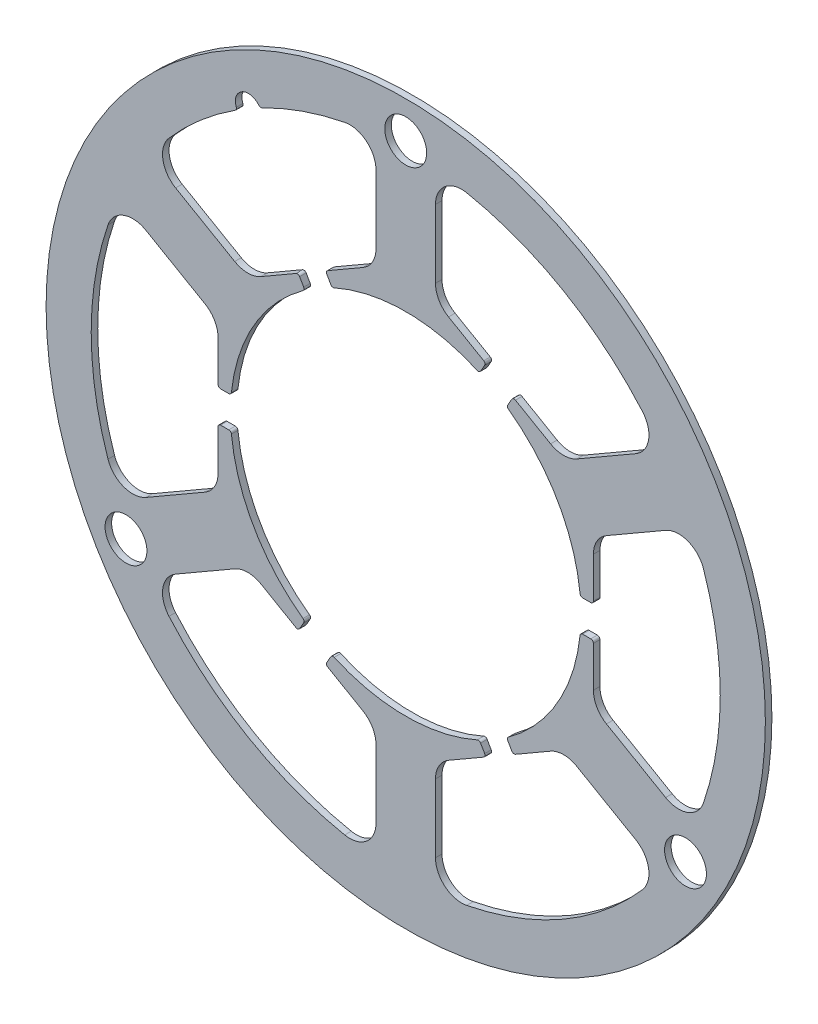
SolidWorks part; units mm, degrees
ref_plane "Ön Düzlem" through (0, 0, 0) normal (0, 0, 1) x (1, 0, 0)
ref_plane "Üst Düzlem" through (0, 0, 0) normal (0, 1, 0) x (1, 0, 0)
ref_plane "Sağ Düzlem" through (0, 0, 0) normal (1, 0, 0) x (0, 0, -1)
sketch "Çizim1" plane through (0, 0, 0) normal (0, 0, 1) x (1, 0, 0)
  line L0 (5.9626, 13.1275) -> (3.275, 14.6791)
  line L1 (3.275, -14.6791) -> (5.9626, -13.1275)
  line L2 (14.35, -4.5033) -> (14.35, -1.4)
  line L3 (11.075, 10.1758) -> (8.3874, 11.7275)
  line L4 (-3.275, 14.6791) -> (-5.9626, 13.1275)
  line L5 (-14.35, 4.5033) -> (-14.35, 1.4)
  line L6 (-11.075, -10.1758) -> (-8.3874, -11.7275)
  line L8 (8.3874, -11.7275) -> (11.075, -10.1758)
  line L9 (-5.9626, -13.1275) -> (-3.275, -14.6791)
  line L10 (-14.35, -1.4) -> (-14.35, -4.5033)
  line L11 (-2.275, 16.4112) -> (-2.275, 21.6316)
  line L12 (-8.1142, 11.6543) -> (-7.8031, 11.1154)
  line L13 (-6.0358, 12.8543) -> (-5.7246, 12.3154)
  line L14 (6.0358, 12.8543) -> (5.7246, 12.3154)
  line L15 (8.1142, 11.6543) -> (7.8031, 11.1154)
  line L16 (14.15, 1.2) -> (13.5277, 1.2)
  line L17 (14.15, -1.2) -> (13.5277, -1.2)
  line L18 (8.1142, -11.6543) -> (7.8031, -11.1154)
  line L19 (6.0358, -12.8543) -> (5.7246, -12.3154)
  line L20 (-6.0358, -12.8543) -> (-5.7246, -12.3154)
  line L21 (-8.1142, -11.6543) -> (-7.8031, -11.1154)
  line L22 (-14.15, -1.2) -> (-13.5277, -1.2)
  line L23 (-14.15, 1.2) -> (-13.5277, 1.2)
  line L24 (-8.3874, 11.7275) -> (-11.075, 10.1758)
  line L25 (14.35, 1.4) -> (14.35, 4.5033)
  line L26 (2.275, 16.4112) -> (2.275, 21.6316)
  line L27 (13.075, 10.1758) -> (17.596, 12.786)
  line L28 (15.35, 6.2354) -> (19.871, 8.8456)
  line L29 (15.35, -6.2354) -> (19.871, -8.8456)
  line L30 (13.075, -10.1758) -> (17.596, -12.786)
  line L31 (2.275, -16.4112) -> (2.275, -21.6316)
  line L32 (-2.275, -16.4112) -> (-2.275, -21.6316)
  line L33 (-13.075, -10.1758) -> (-17.596, -12.786)
  line L34 (-15.35, -6.2354) -> (-19.871, -8.8456)
  line L35 (-15.35, 6.2354) -> (-19.871, 8.8456)
  line L36 (-13.075, 10.1758) -> (-17.596, 12.786)
  circle A0 centre (0, 0) radius 27.5
  arc A1 (-4.6628, 23.5937) -> (-10.9904, 21.3919) centre (0, 0) ccw
  arc A3 (-7.859, 10.8534) -> (-13.3288, 1.3794) centre (0, 0) ccw
  arc A4 (5.4698, 12.2328) -> (-5.4698, 12.2328) centre (0, 0) ccw
  arc A7 (13.3288, 1.3794) -> (7.859, 10.8534) centre (0, 0) ccw
  arc A8 (7.859, -10.8534) -> (13.3288, -1.3794) centre (0, 0) ccw
  arc A10 (-5.4698, -12.2328) -> (5.4698, -12.2328) centre (0, 0) ccw
  arc A12 (-13.3288, -1.3794) -> (-7.859, -10.8534) centre (0, 0) ccw
  arc A14 (18.1013, 15.8349) -> (4.6628, 23.5937) centre (0, 0) ccw
  arc A15 (22.7641, -7.7588) -> (22.7641, 7.7588) centre (0, 0) ccw
  arc A16 (4.6628, -23.5937) -> (18.1013, -15.8349) centre (0, 0) ccw
  arc A17 (-18.1013, -15.8349) -> (-4.6628, -23.5937) centre (0, 0) ccw
  arc A18 (-22.7641, 7.7588) -> (-22.7641, -7.7588) centre (0, 0) ccw
  arc A19 (-15.35, 6.2354) -> (-14.35, 4.5033) centre (-16.35, 4.5033) cw
  arc A20 (-19.871, 8.8456) -> (-22.7641, 7.7588) centre (-20.871, 7.1136) ccw
  arc A21 (-15.35, -6.2354) -> (-14.35, -4.5033) centre (-16.35, -4.5033) ccw
  arc A22 (-19.871, -8.8456) -> (-22.7641, -7.7588) centre (-20.871, -7.1136) cw
  arc A23 (-13.075, -10.1758) -> (-11.075, -10.1758) centre (-12.075, -11.9078) cw
  arc A24 (-17.596, -12.786) -> (-18.1013, -15.8349) centre (-16.596, -14.5181) ccw
  arc A25 (-2.275, -16.4112) -> (-3.275, -14.6791) centre (-4.275, -16.4112) ccw
  arc A26 (-2.275, -21.6316) -> (-4.6628, -23.5937) centre (-4.275, -21.6316) cw
  arc A27 (2.275, -16.4112) -> (3.275, -14.6791) centre (4.275, -16.4112) cw
  arc A28 (2.275, -21.6316) -> (4.6628, -23.5937) centre (4.275, -21.6316) ccw
  arc A29 (13.075, -10.1758) -> (11.075, -10.1758) centre (12.075, -11.9078) ccw
  arc A30 (17.596, -12.786) -> (18.1013, -15.8349) centre (16.596, -14.5181) cw
  arc A31 (15.35, -6.2354) -> (14.35, -4.5033) centre (16.35, -4.5033) cw
  arc A32 (19.871, -8.8456) -> (22.7641, -7.7588) centre (20.871, -7.1136) ccw
  arc A33 (19.871, 8.8456) -> (22.7641, 7.7588) centre (20.871, 7.1136) cw
  arc A34 (15.35, 6.2354) -> (14.35, 4.5033) centre (16.35, 4.5033) ccw
  arc A35 (13.075, 10.1758) -> (11.075, 10.1758) centre (12.075, 11.9078) cw
  arc A36 (17.596, 12.786) -> (18.1013, 15.8349) centre (16.596, 14.5181) ccw
  arc A37 (2.275, 16.4112) -> (3.275, 14.6791) centre (4.275, 16.4112) ccw
  arc A38 (2.275, 21.6316) -> (4.6628, 23.5937) centre (4.275, 21.6316) cw
  arc A39 (-2.275, 16.4112) -> (-3.275, 14.6791) centre (-4.275, 16.4112) cw
  arc A40 (-13.075, 10.1758) -> (-11.075, 10.1758) centre (-12.075, 11.9078) ccw
  arc A41 (-17.596, 12.786) -> (-18.1013, 15.8349) centre (-16.596, 14.5181) cw
  arc A42 (-2.275, 21.6316) -> (-4.6628, 23.5937) centre (-4.275, 21.6316) ccw
  circle A43 centre (0, 24.7) radius 1.6
  circle A44 centre (21.3908, -12.35) radius 1.6
  circle A45 centre (-21.3908, -12.35) radius 1.6
  arc A46 (-11.239, 21.4461) -> (-12.9534, 20.4563) centre (-12.025, 20.8279) ccw
  arc A47 (-13.0307, 20.2139) -> (-18.1013, 15.8349) centre (0, 0) ccw
  arc A48 (-13.5277, 1.2) -> (-13.3288, 1.3794) centre (-13.5277, 1.4) ccw
  arc A49 (-14.35, 1.4) -> (-14.15, 1.2) centre (-14.15, 1.4) ccw
  arc A50 (-14.35, -1.4) -> (-14.15, -1.2) centre (-14.15, -1.4) cw
  arc A51 (-13.5277, -1.2) -> (-13.3288, -1.3794) centre (-13.5277, -1.4) cw
  arc A52 (-8.3874, -11.7275) -> (-8.1142, -11.6543) centre (-8.2874, -11.5543) ccw
  arc A53 (-7.8031, -11.1154) -> (-7.859, -10.8534) centre (-7.9763, -11.0154) ccw
  arc A54 (-5.9626, -13.1275) -> (-6.0358, -12.8543) centre (-5.8626, -12.9543) cw
  arc A55 (-5.7246, -12.3154) -> (-5.4698, -12.2328) centre (-5.5514, -12.4154) cw
  arc A56 (5.7246, -12.3154) -> (5.4698, -12.2328) centre (5.5514, -12.4154) ccw
  arc A57 (5.9626, -13.1275) -> (6.0358, -12.8543) centre (5.8626, -12.9543) ccw
  arc A58 (8.3874, -11.7275) -> (8.1142, -11.6543) centre (8.2874, -11.5543) cw
  arc A59 (7.8031, -11.1154) -> (7.859, -10.8534) centre (7.9763, -11.0154) cw
  arc A60 (14.35, -1.4) -> (14.15, -1.2) centre (14.15, -1.4) ccw
  arc A61 (13.5277, -1.2) -> (13.3288, -1.3794) centre (13.5277, -1.4) ccw
  arc A62 (13.5277, 1.2) -> (13.3288, 1.3794) centre (13.5277, 1.4) cw
  arc A63 (14.35, 1.4) -> (14.15, 1.2) centre (14.15, 1.4) cw
  arc A64 (7.8031, 11.1154) -> (7.859, 10.8534) centre (7.9763, 11.0154) ccw
  arc A65 (8.3874, 11.7275) -> (8.1142, 11.6543) centre (8.2874, 11.5543) ccw
  arc A66 (5.7246, 12.3154) -> (5.4698, 12.2328) centre (5.5514, 12.4154) cw
  arc A67 (6.0358, 12.8543) -> (5.9626, 13.1275) centre (5.8626, 12.9543) ccw
  arc A68 (-5.9626, 13.1275) -> (-6.0358, 12.8543) centre (-5.8626, 12.9543) ccw
  arc A69 (-5.7246, 12.3154) -> (-5.4698, 12.2328) centre (-5.5514, 12.4154) ccw
  arc A70 (-7.8031, 11.1154) -> (-7.859, 10.8534) centre (-7.9763, 11.0154) cw
  arc A71 (-8.3874, 11.7275) -> (-8.1142, 11.6543) centre (-8.2874, 11.5543) cw
  arc A72 (-12.9534, 20.4563) -> (-13.0307, 20.2139) centre (-13.1391, 20.382) cw
  arc A73 (-11.239, 21.4461) -> (-10.9904, 21.3919) centre (-11.0818, 21.5698) ccw
  point P29 (0, 0)
  point P51 (0, 0)
  point P72 (0, 0)
  point P123 (0, 0)
  point P173 (-6.1358, 13.0275)
  point P176 (-5.6338, 12.1581)
  point P179 (-7.7123, 10.9581)
  point P182 (-8.2142, 11.8275)
  point P185 (-12.8804, 20.31)
  dimension "D1" = 55
  dimension "D2" = 48.1
  dimension "D4" = 26.8
  dimension "D12" = 2
  dimension "D13" = 3.2
  dimension "D14" = 1.2
  dimension "D16" = 2
  dimension "D18" = 0.2
  dimension "D3" = 28.7
  dimension "D5" = 2.4
  dimension "D7" = 6
  dimension "D8" = 2.275
  dimension "D6" = 2.4
  dimension "D9" = 4.55
  dimension "D10" = 120
  dimension "D11" = 6
  dimension "D17" = 30
  dimension "D19" = 2.4
  dimension "D20" = 2.4
  dimension "D15" = 3
extrude "Yükseklik-Ekstrüzyon1" add sketch "Çizim1" along normal blind 0.5
